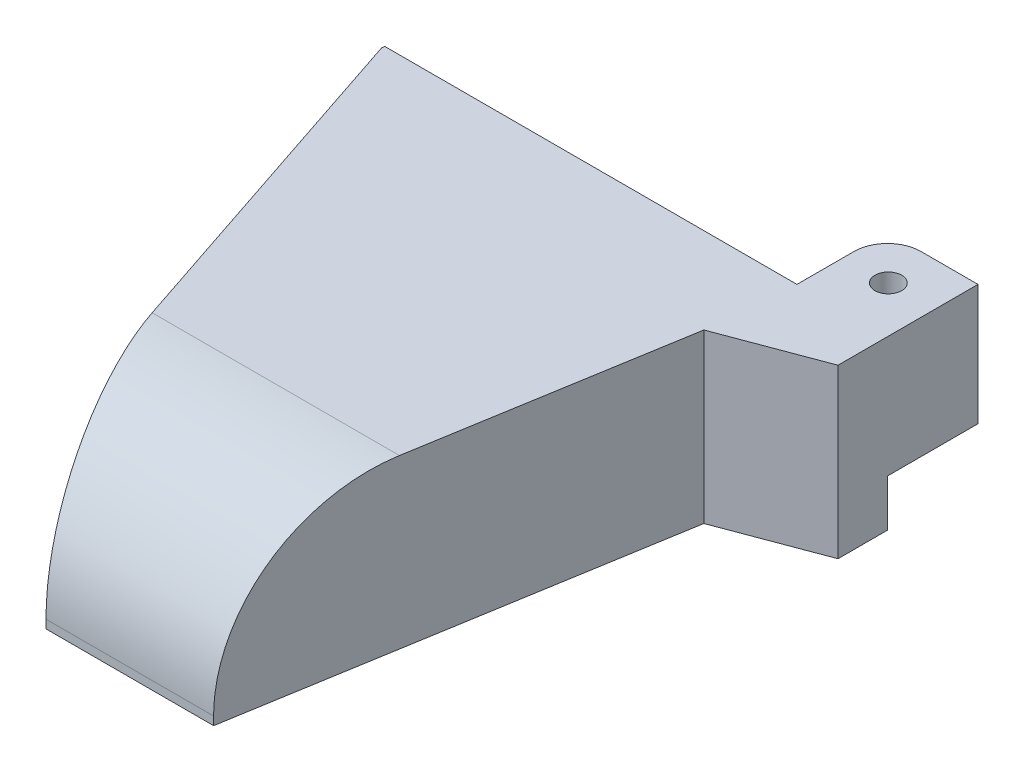
SolidWorks part; units mm, degrees
ref_plane "前视基准面" through (0, 0, 0) normal (0, 0, 1) x (1, 0, 0)
ref_plane "上视基准面" through (0, 0, 0) normal (0, 1, 0) x (1, 0, 0)
ref_plane "右视基准面" through (0, 0, 0) normal (1, 0, 0) x (0, 0, -1)
other "Configuration Table"
sketch "草图1" plane through (0, 0, 0) normal (0, 1, 0) x (1, 0, 0)
  line L1 (0, 0) -> (30, 0)
  line L2 (0, 0) -> (0, -6)
  line L3 (0, -6) -> (30, -6)
  line L4 (30, 0) -> (30, -6)
  dimension "D1" = 30
  dimension "D2" = 6
extrude "凸台-拉伸1" add sketch "草图1" along normal blind 2
sketch "草图2" plane through (0, 2, 0) normal (0, 1, 0) x (1, 0, 0)
  line L0 (30, -6) -> (30, 0) construction
  line L1 (30, 0) -> (0, 0) construction
  circle A0 centre (27.25, -3) radius 0.8
  dimension "D2" = 1.6
  dimension "D3" = 3
  dimension "D1" = 2.75
extrude "切除-拉伸1" cut sketch "草图2" against normal blind 2
sketch "草图3" plane through (0, 2, 0) normal (0, 1, 0) x (1, 0, 0)
  line L0 (0, 0) -> (0, -6) construction
  line L1 (0, -5.8) -> (1.6, -5.8)
  line L2 (0, -5.8) -> (0, -6)
  line L3 (0, -6) -> (1.6, -6)
  line L4 (1.6, -5.8) -> (1.6, -6)
  line L5 (0, -6) -> (30, -6) construction
  line L6 (30, 0) -> (0, 0) construction
  line L7 (30, -6) -> (30, 0) construction
  line L8 (23.4, -6) -> (25, -6)
  line L9 (23.4, -6) -> (23.4, -5.8)
  line L10 (23.4, -5.8) -> (25, -5.8)
  line L11 (25, -6) -> (25, -5.8)
  dimension "D1" = 1.6
  dimension "D2" = 5.8
  dimension "D3" = 5.8
  dimension "D4" = 1.6
  dimension "D5" = 5
extrude "凸台-拉伸2" add sketch "草图3" along normal blind 10
sketch "草图4" plane through (0, 12, 0) normal (0, 1, 0) x (1, 0, 0)
  line L1 (1.6, -5.8) -> (23.4, -5.8)
  line L2 (1.6, -5.8) -> (1.6, -6)
  line L3 (1.6, -6) -> (23.4, -6)
  line L4 (23.4, -5.8) -> (23.4, -6)
extrude "凸台-拉伸3" add sketch "草图4" against normal blind 1.6
sketch "草图5" plane through (0, 2, 0) normal (0, 1, 0) x (1, 0, 0)
  line L1 (25, -5.8) -> (30, -5.8)
  line L2 (25, -5.8) -> (25, -6)
  line L3 (25, -6) -> (30, -6)
  line L4 (30, -5.8) -> (30, -6)
extrude "凸台-拉伸4" add sketch "草图5" along normal blind 10
sketch "草图6" plane through (0, 0, 5.8) normal (0, 0, -1) x (-1, 0, 0)
  line L1 (-30, 12) -> (-24.6, 12)
  line L2 (-30, 12) -> (-30, 4.8)
  line L3 (-30, 4.8) -> (-24.6, 4.8)
  line L4 (-24.6, 12) -> (-24.6, 4.8)
  dimension "D1" = 5.4
  dimension "D2" = 7.2
extrude "凸台-拉伸5" add sketch "草图6" along normal blind 5.4
fillet "圆角1" radius 2 1 edges at (24.6, 8.4, 0.4)
sketch "草图7" plane through (0, 4.8, 0) normal (0, -1, 0) x (-1, 0, 0)
  circle A0 centre (-27.25, -3) radius 0.8
extrude "切除-拉伸2" cut sketch "草图7" against normal through all
sketch "草图8" plane through (0, 0, 0) normal (-1, 0, 0) x (0, 0, 1)
  line L1 (0, 2) -> (6, 2)
  line L2 (0, 2) -> (0, 0)
  line L3 (0, 0) -> (6, 0)
  line L4 (6, 2) -> (6, 0)
extrude "切除-拉伸3" cut sketch "草图8" against normal through all
sketch "草图9" plane through (0, 0, 6) normal (0, 0, 1) x (1, 0, 0)
  line L0 (23.4, 10.4) -> (23.4, 2) construction
  line L1 (1.6, 2) -> (23.4, 2)
  line L2 (1.6, 2) -> (1.6, 3.6)
  line L3 (1.6, 3.6) -> (23.4, 3.6)
  line L4 (23.4, 2) -> (23.4, 3.6)
  dimension "D1" = 1.6
extrude "凸台-拉伸7" add sketch "草图9" against normal up to surface (0.2 mm away) up to face at (15.92, 6.24, 5.8)
ref_plane "分割" through (0, 0, 6) normal (0, 0, 1) x (1, 0, 0)
sketch "草图11" plane through (0, 2, 0) normal (0, -1, 0) x (-1, 0, 0)
  line L0 (0, -6) -> (-10, -36)
  line L1 (-10, -36) -> (-20, -36)
  line L2 (-20, -36) -> (-25, -6)
  line L3 (0, -6) -> (-30, -6) construction
  line L4 (-25, -6) -> (0, -6)
  point P7 (-15, -36)
  dimension "D3" = 30
  dimension "D1" = 1.6
  dimension "D4" = 10
  dimension "D2" = 15
extrude "凸台-拉伸9" add sketch "草图11" against normal blind 1.6
sketch "草图12" plane through (0, 3.6, 0) normal (0, 1, 0) x (1, 0, 0)
  line L11 (2.2199, -7.6) -> (11.1532, -34.4)
  line L12 (11.1532, -34.4) -> (18.6446, -34.4)
  line L13 (18.6446, -34.4) -> (23.1113, -7.6)
  line L16 (23.4, -5.8) -> (1.6, -5.8)
  line L17 (1.6, -5.8) -> (1.6, -6)
  line L18 (1.6, -6) -> (0, -6)
  line L19 (0, -6) -> (10, -36)
  line L20 (10, -36) -> (20, -36)
  line L21 (20, -36) -> (25, -6)
  line L22 (25, -6) -> (23.4, -6)
  line L23 (23.4, -6) -> (23.4, -5.8)
  line L26 (1.6, -6) -> (0, -6)
  line L27 (0, -6) -> (10, -36)
  line L28 (10, -36) -> (20, -36)
  line L29 (20, -36) -> (25, -6)
  line L30 (25, -6) -> (23.4, -6)
  line L32 (2.2199, -7.6) -> (1.6, -6)
  line L33 (23.1113, -7.6) -> (23.4, -6)
  line L35 (21.8, -7.4) -> (3.2, -7.4) construction
  line L36 (21.8, -7.6) -> (21.8, -7.4) construction
  line L37 (23.1113, -7.6) -> (21.8, -7.6) construction
  line L38 (23.4, -5.8) -> (1.6, -5.8) construction
  line L39 (23.4, -6) -> (23.4, -5.8) construction
  line L40 (3.2, -7.6) -> (2.2199, -7.6) construction
  line L41 (3.2, -7.4) -> (3.2, -7.6) construction
  line L42 (1.6, -5.8) -> (1.6, -6) construction
  dimension "D1" = 0
  dimension "D2" = 1.6
extrude "凸台-拉伸10" add sketch "草图12" along normal up to surface (8.4 mm away) up to face at (27.25, 12, 2.2)
sketch "草图13" plane through (0, 12, 0) normal (0, 1, 0) x (1, 0, 0)
  line L16 (1.6, -5.8) -> (1.6, -6)
  line L17 (1.6, -6) -> (2.2199, -7.6)
  line L18 (2.2199, -7.6) -> (11.1532, -34.4)
  line L19 (11.1532, -34.4) -> (18.6446, -34.4)
  line L20 (18.6446, -34.4) -> (23.1113, -7.6)
  line L21 (23.1113, -7.6) -> (23.4, -6)
  line L22 (23.4, -6) -> (23.4, -5.8)
  line L23 (23.4, -5.8) -> (1.6, -5.8)
  line L24 (1.6, -5.8) -> (1.6, -6)
  line L25 (1.6, -6) -> (2.2199, -7.6)
  line L26 (2.2199, -7.6) -> (11.1532, -34.4)
  line L27 (11.1532, -34.4) -> (18.6446, -34.4)
  line L28 (18.6446, -34.4) -> (23.1113, -7.6)
  line L29 (23.1113, -7.6) -> (23.4, -6)
  line L30 (23.4, -6) -> (23.4, -5.8)
  line L31 (23.4, -5.8) -> (1.6, -5.8)
  dimension "D1" = 0
extrude "凸台-拉伸11" add sketch "草图13" against normal blind 1.6
sketch "草图15" plane through (0, 2, 0) normal (0, -1, 0) x (1, 0, 0)
  line L0 (11.1532, 34.4) -> (18.6446, 34.4)
  line L1 (18.6446, 34.4) -> (19.3113, 30.4)
  line L2 (19.3113, 30.4) -> (9.8199, 30.4)
  line L3 (9.8199, 30.4) -> (11.1532, 34.4)
  line L4 (20, 36) -> (10, 36) construction
  line L5 (10, 36) -> (0, 6) construction
  line L6 (22.5, 21) -> (20, 36) construction
  dimension "D1" = 1.6
  dimension "D2" = 180
  dimension "D3" = 180
  dimension "D4" = 1.6
  dimension "D5" = 1.6
  dimension "D6" = 4
extrude "切除-拉伸4" cut sketch "草图15" against normal blind 1.6
fillet "圆角2" radius 9 1 edges at (14.8989, 10.4, 34.4)
fillet "圆角3" radius 9.5 1 edges at (15, 12, 36)
fillet "圆角4" radius 1 1 edges at (14.5656, 3.6, 30.4)
chamfer "倒角1" distance 5 angle 60 1 edges at (25, 7, 6) first distance on face at (22.2511, 6.4935, 22.4935)
equation "\"D2@草图11\"=15"
